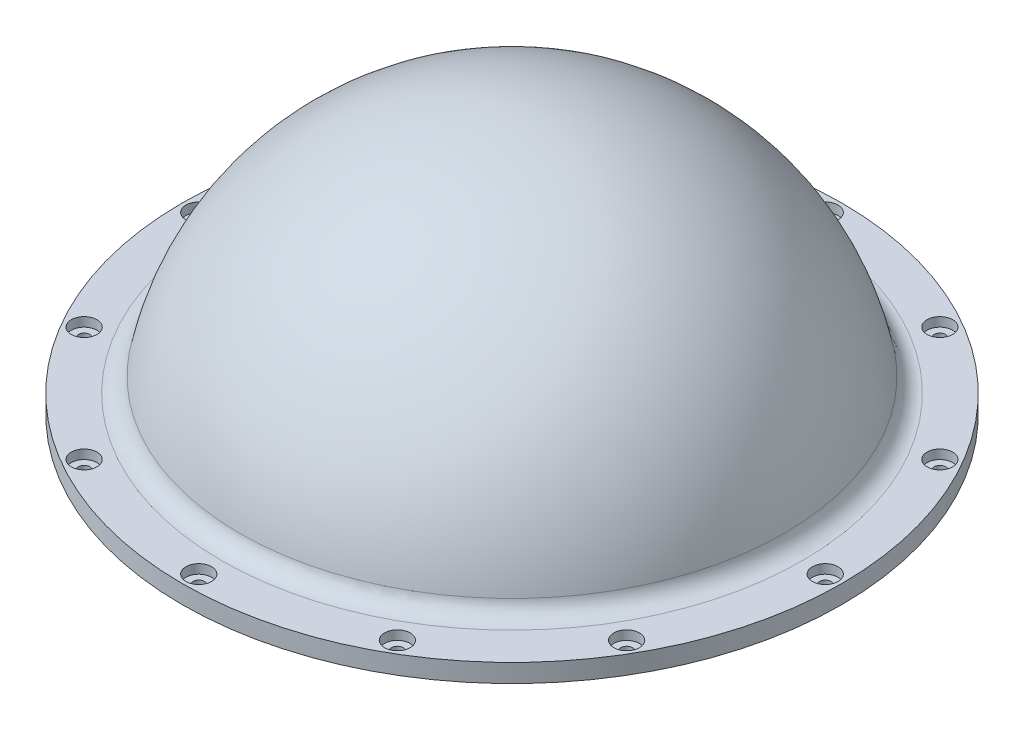
SolidWorks part; units mm, degrees
ref_plane "Front Plane" through (0, 0, 0) normal (0, 0, 1) x (1, 0, 0)
ref_plane "Top Plane" through (0, 0, 0) normal (0, 1, 0) x (1, 0, 0)
ref_plane "Right Plane" through (0, 0, 0) normal (1, 0, 0) x (0, 0, -1)
sketch "Sketch1" plane through (0, 0, 0) normal (0, 1, 0) x (1, 0, 0)
  circle A0 centre (0, 0) radius 90
  circle A1 centre (0, 0) radius 71.5
  circle A2 centre (0, 0) radius 85.5 construction
  circle A3 centre (0, 85.5) radius 1.55
  circle A4 centre (0, 85.5) radius 3.5
  circle A5 centre (42.75, 74.0452) radius 3.5
  circle A6 centre (42.75, 74.0452) radius 1.55
  circle A7 centre (74.0452, 42.75) radius 3.5
  circle A8 centre (74.0452, 42.75) radius 1.55
  circle A9 centre (85.5, 0) radius 3.5
  circle A10 centre (85.5, 0) radius 1.55
  circle A11 centre (74.0452, -42.75) radius 3.5
  circle A12 centre (74.0452, -42.75) radius 1.55
  circle A13 centre (42.75, -74.0452) radius 3.5
  circle A14 centre (42.75, -74.0452) radius 1.55
  circle A15 centre (0, -85.5) radius 3.5
  circle A16 centre (0, -85.5) radius 1.55
  circle A17 centre (-42.75, -74.0452) radius 3.5
  circle A18 centre (-42.75, -74.0452) radius 1.55
  circle A19 centre (-74.0452, -42.75) radius 3.5
  circle A20 centre (-74.0452, -42.75) radius 1.55
  circle A21 centre (-85.5, 0) radius 3.5
  circle A22 centre (-85.5, 0) radius 1.55
  circle A23 centre (-74.0452, 42.75) radius 3.5
  circle A24 centre (-74.0452, 42.75) radius 1.55
  circle A25 centre (-42.75, 74.0452) radius 3.5
  circle A26 centre (-42.75, 74.0452) radius 1.55
  point P44 (0, 0)
  dimension "D1" = 180
  dimension "D2" = 143
  dimension "D3" = 171
  dimension "D4" = 3.1
  dimension "D5" = 7
  dimension "D7" = 85.5
  dimension "D8" = 85.5
  dimension "D6" = 12
extrude "Boss-Extrude1" add sketch "Sketch1" against normal blind 5 contours A0 A25 A23 A21 A19 A17 A15 A13 A11 A9 A7 A5 A4 A1 | A17 | A19 | A21 | A15 | A23 | A25 | A13 | A11 | A9 | A7 | A4 | A5 region at (-89.7454, 0, 0)
extrude "Cut-Extrude1" cut sketch "Sketch1<4>" against normal up to surface (5 mm away) contours A16 | A20 | A18 | A22 | A24 | A26 | A3 | A6 | A8 | A10 | A12 | A14 region at (0, 0, -85.5) region at (42.75, 0, -74.0452) region at (74.0452, 0, -42.75) region at (85.5, 0, 0) region at (74.0452, 0, 42.75) region at (42.75, 0, 74.0452) region at (0, 0, 85.5) region at (-42.75, 0, 74.0452) region at (-74.0452, 0, 42.75) region at (-85.5, 0, 0) region at (-74.0452, 0, -42.75) region at (-42.75, 0, -74.0452) up to face at (0, -5, 71.5)
sketch "Sketch1<4>" plane through (0, 0, 0) normal (0, 1, 0) x (1, 0, 0) same geometry as "Sketch1"
extrude "Cut-Extrude2" cut sketch "Sketch1<5>" against normal blind 2.5 contours A19 A20 | A21 A22 | A17 A18 | A15 A16 | A23 A24 | A25 A26 | A4 A3 | A7 A8 | A5 A6 | A11 A12 | A9 A10 | A13 A14 region at (-3.401, 0, -85.5) region at (39.349, 0, -74.0452) region at (70.6442, 0, -42.75) region at (82.099, 0, 0) region at (70.6442, 0, 42.75) region at (39.349, 0, 74.0452) region at (-3.401, 0, 85.5) region at (-46.151, 0, 74.0452) region at (-77.4462, 0, 42.75) region at (-88.901, 0, 0) region at (-77.4462, 0, -42.75) region at (-46.151, 0, -74.0452)
sketch "Sketch1<5>" plane through (0, 0, 0) normal (0, 1, 0) x (1, 0, 0) same geometry as "Sketch1"
sketch "Sketch2" plane through (0, 0, 0) normal (0, 0, 1) x (1, 0, 0)
  line L0 (0, 0) -> (0, 65) construction
  line L1 (-90, -5) -> (90, -5) construction
  line L3 (0, 65) -> (0, 62)
  line L4 (75, 0) -> (72, 0)
  arc A0 (0, 65) -> (75, 0) centre (0, -10.7692) cw
  arc A1 (0, 62) -> (72, 0) centre (0, -10.8065) cw
  point P6 (0, 0)
  dimension "D1" = 70
  dimension "D2" = 72
  dimension "D3" = 3
  dimension "D4" = 3
revolve "Revolve1" add sketch "Sketch2" angle 360 about L0
fillet "Fillet1" radius 5 2 edges at (0, 0, 75) (0, -5, 71.5)
